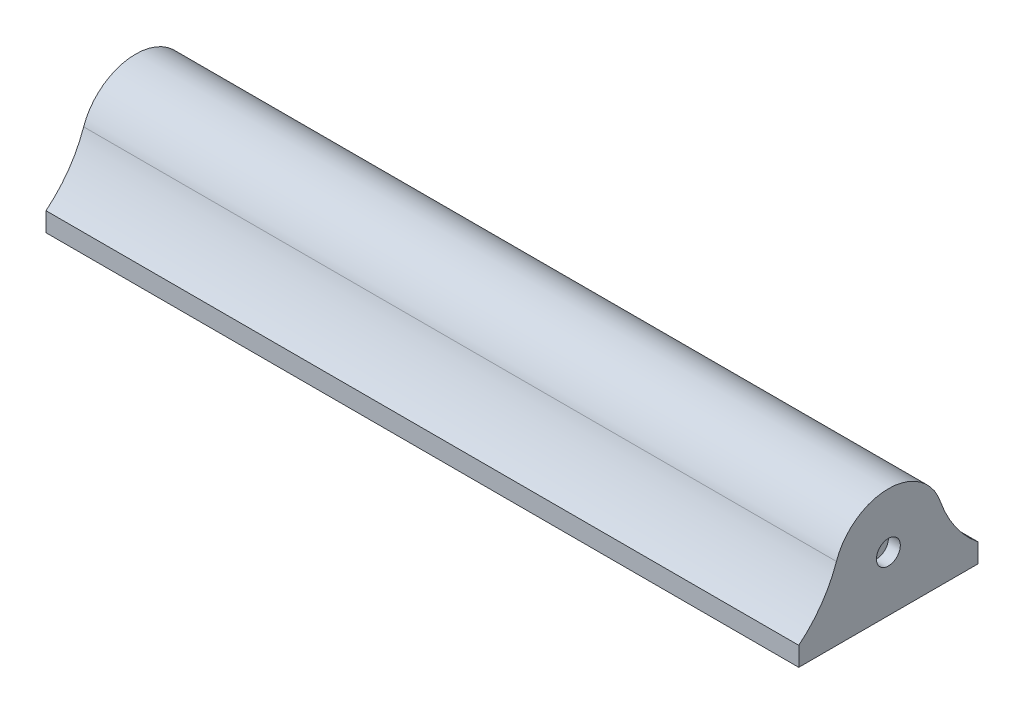
SolidWorks part; units mm, degrees
ref_plane "Front Plane" through (0, 0, 0) normal (0, 0, 1) x (1, 0, 0)
ref_plane "Top Plane" through (0, 0, 0) normal (0, 1, 0) x (1, 0, 0)
ref_plane "Right Plane" through (0, 0, 0) normal (1, 0, 0) x (0, 0, -1)
sketch "Sketch2" plane through (0, 0, 0) normal (1, 0, 0) x (0, 0, -1)
  line L0 (7.5, 0) -> (-7.5, 0)
  line L1 (-7.5, 0) -> (-7.5, 1.6)
  line L2 (-7.5, 1.6) -> (-4.6, 1.6)
  line L3 (0, 0) -> (0, 7.3722) construction
  line L4 (7.5, 1.6) -> (4.6, 1.6)
  line L5 (7.5, 0) -> (7.5, 1.6)
  line L6 (0, 1.6) -> (2.1738, 1.6) construction
  line L7 (-4.6, 1.6) -> (-4.6, 4.6)
  line L8 (4.6, 1.6) -> (4.6, 4.6)
  circle A0 centre (0, 4.6) radius 3
  arc A1 (-4.6, 4.6) -> (4.6, 4.6) centre (0, 4.6) cw
  point P15 (-6.1152, 0)
  point P16 (-4.5, 1.6)
  dimension "D1" = 6
  dimension "D2" = 4.6
  dimension "D3" = 1.6
  dimension "D4" = 1.6
  dimension "D5" = 15
extrude "Boss-Extrude1" add sketch "Sketch2" along normal blind 63
fillet "Fillet1" radius 10 2 edges at (31.5, 1.6, 4.6) (31.5, 1.6, -4.6)
sketch "Sketch4" plane through (0, 0, 0) normal (0, 0, 1) x (1, 0, 0)
  line L0 (62, 7.6) -> (63, 7.6)
  line L1 (63, 7.6) -> (63, 5.6)
  line L2 (63, 5.6) -> (62, 5.6)
  line L3 (62, 5.6) -> (62, 7.6)
  line L5 (63, 6.1015) -> (63, 9.2) construction
  line L6 (63, 4.6) -> (62.3639, 4.6) construction
  line L7 (63, 1.6) -> (63, 7.6) construction
  point P2 (63, 7.9745)
  point P6 (68.7383, 4.3356)
  point P7 (0, 0)
  point P10 (74.2521, 5.5791)
  dimension "D1" = 1
  dimension "D3" = 1
revolve "Revolve1" add sketch "Sketch4" angle 360 about L6
pattern_linear "LPattern1" count 27 spacing 2 along (-1, 0, 0) of "Revolve1"
